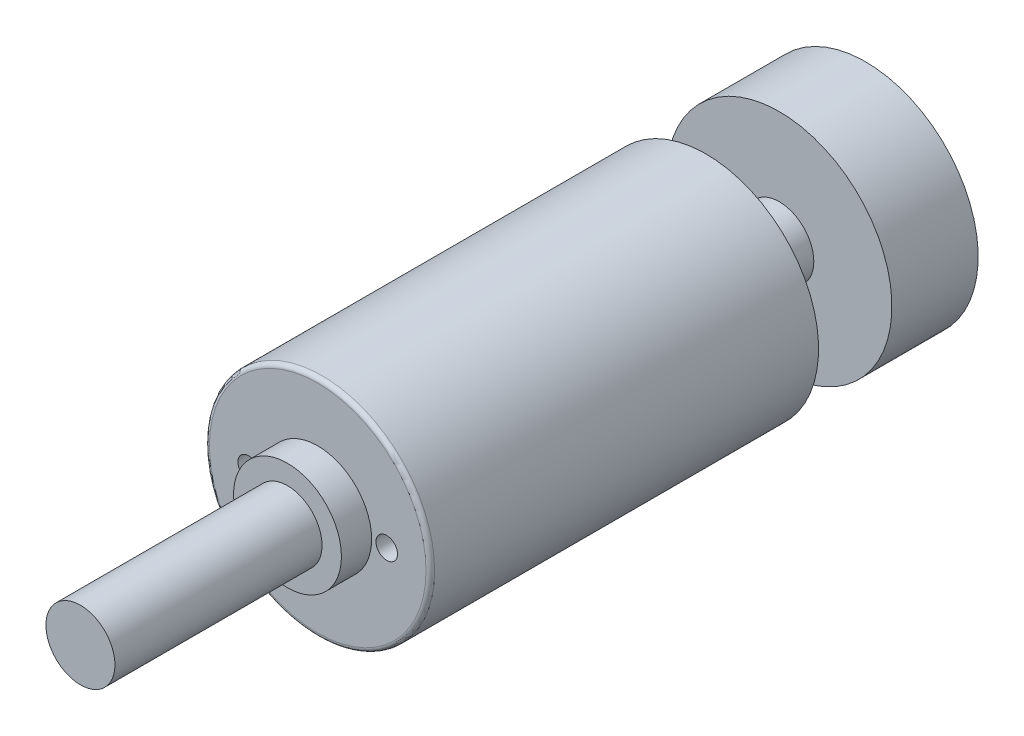
SolidWorks part; units mm, degrees
ref_plane "前视基准面" through (0, 0, 0) normal (0, 0, 1) x (1, 0, 0)
ref_plane "上视基准面" through (0, 0, 0) normal (0, 1, 0) x (1, 0, 0)
ref_plane "右视基准面" through (0, 0, 0) normal (1, 0, 0) x (0, 0, -1)
sketch "草图1" plane through (0, 0, 0) normal (0, 0, 1) x (1, 0, 0)
  circle A0 centre (0, 0) radius 26.1
  dimension "D1" = 52.2
extrude "凸台-拉伸1" add sketch "草图1" along normal blind 90
fillet "圆角1" radius 1 1 edges at (26.1, 0, 90)
sketch "草图2" plane through (0, 0, 90) normal (0, 0, 1) x (1, 0, 0)
  circle A0 centre (0, 0) radius 12.5
  dimension "D1" = 25
extrude "凸台-拉伸2" add sketch "草图2" along normal blind 7
sketch "草图3" plane through (0, 0, 97) normal (0, 0, 1) x (1, 0, 0)
  circle A0 centre (0, 0) radius 8
extrude "凸台-拉伸3" add sketch "草图3" along normal blind 48
sketch "草图4" plane through (0, 0, 90) normal (0, 0, 1) x (1, 0, 0)
  circle A0 centre (0, 0) radius 16 construction
  circle A1 centre (-16, 0) radius 2.5
  circle A2 centre (16, 0) radius 2.5
  dimension "D1" = 5
  dimension "D2" = 5
extrude "切除-拉伸1" cut sketch "草图4" against normal blind 5
extrude "凸台-拉伸4" add sketch "草图1<2>" along normal blind 10
sketch "草图1<2>" plane through (0, 0, 0) normal (0, 0, 1) x (1, 0, 0) same geometry as "草图1"
sketch "草图6" plane through (0, 0, 0) normal (0, 0, -1) x (-1, 0, 0)
  circle A0 centre (0, 0) radius 8
extrude "凸台-拉伸5" add sketch "草图6" along normal blind 17
sketch "草图7" plane through (0, 0, -17) normal (0, 0, -1) x (-1, 0, 0)
  circle A0 centre (0, 0) radius 26.1
extrude "凸台-拉伸6" add sketch "草图7" along normal blind 20
